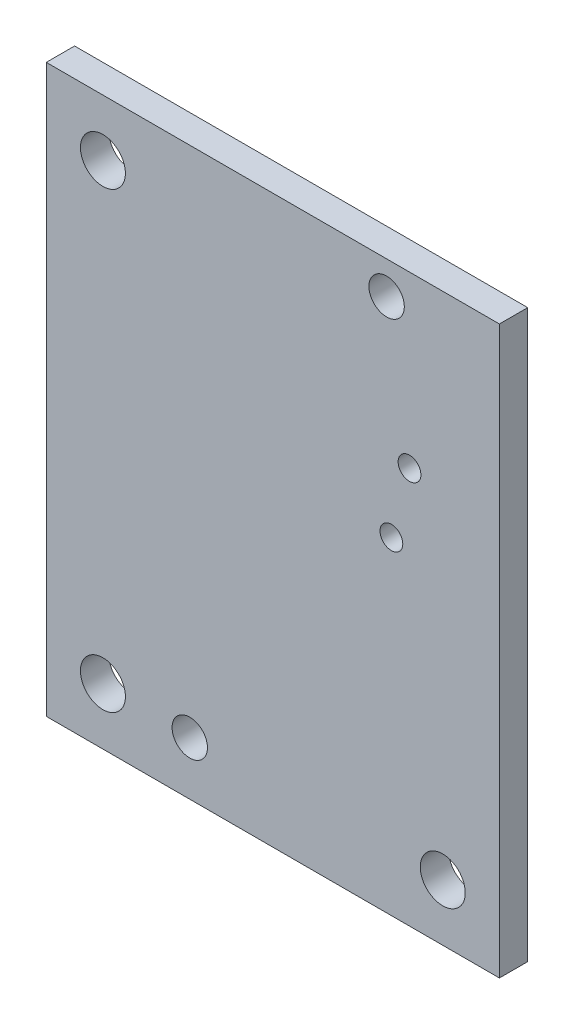
SolidWorks part; units mm, degrees
ref_plane "Front Plane" through (0, 0, 0) normal (1, 0, 0) x (0, 1, 0)
ref_plane "Top Plane" through (0, 0, 0) normal (0, 0, 1) x (0, 1, 0)
ref_plane "Right Plane" through (0, 0, 0) normal (0, 1, 0) x (-1, 0, 0)
sketch "Sketch2" plane through (0, 0, 0) normal (0, 0, 1) x (0, 1, 0)
  line L1 (0, 0) -> (127, 0)
  line L2 (0, 0) -> (0, 101.6)
  line L3 (0, 101.6) -> (127, 101.6)
  line L4 (127, 0) -> (127, 101.6)
  line L5 (12.7, 88.9) -> (114.3, 88.9) construction
  line L6 (12.7, 88.9) -> (12.7, 12.7) construction
  line L7 (12.7, 12.7) -> (114.3, 12.7) construction
  line L8 (114.3, 88.9) -> (114.3, 12.7) construction
  line L9 (12.7, 12.7) -> (73.436, 12.7) construction
  line L10 (12.7, 12.7) -> (12.7, 24.2176) construction
  line L11 (12.7, 24.2176) -> (73.436, 24.2176) construction
  line L12 (73.436, 12.7) -> (73.436, 24.2176) construction
  line L13 (12.7, 12.7) -> (88.9, 12.7) construction
  line L14 (12.7, 12.7) -> (12.7, 20.1554) construction
  line L15 (12.7, 20.1554) -> (88.9, 20.1554) construction
  line L16 (88.9, 12.7) -> (88.9, 20.1554) construction
  point P12 (12.7, 45.9336)
  point P16 (85.9042, 45.6317)
  dimension "D1" = 12.7
  dimension "D2" = 12.7
  dimension "D3" = 12.7
  dimension "D4" = 12.7
  dimension "D5" = 127
  dimension "D6" = 101.6
  dimension "D7" = 11.5176
  dimension "D8" = 60.736
  dimension "D9" = 7.4554
  dimension "D10" = 76.2
extrude "Boss-Extrude1" add sketch "Sketch2" along normal blind 6.35
hole_wizard "3/8 Clearance Hole1" positions "Sketch3" profile "Sketch4" hole size "3/8" standard "ANSI Inch" end condition through all
sketch "Sketch3" plane through (0, 0, 6.35) normal (0, 0, 1) x (1, 0, 0)
  point P0 (-12.7, 12.7)
  point P3 (-88.9, 12.7)
  point P6 (-88.9, 114.3)
sketch "Sketch4" plane through (-12.7, 12.7, 6.35) normal (1, 0, 0) x (0, -1, 0)
  line L0 (0, 0) -> (0, 6.35)
  line L1 (0, 6.35) -> (5.0419, 6.35)
  line L2 (5.0419, 6.35) -> (5.0419, 0)
  line L5 (5.0419, 0) -> (0, 0)
  line L11 (0, -6.35) -> (0, 107.95) construction
  dimension "Thru Hole Dia." = 10.0838
  dimension "Thru Hole Depth" = 6.35
hole_wizard "Tap Drill for 1/4-20 Tap1" positions "Sketch7" profile "Sketch6" hole size "1/4-20" standard "ANSI Inch" end condition through all
sketch "Sketch7" plane through (0, 0, 6.35) normal (0, 0, 1) x (1, 0, 0)
  point P0 (-24.2176, 73.436)
  point P3 (-20.1554, 88.9)
sketch "Sketch6" plane through (-24.2176, 73.436, 6.35) normal (1, 0, 0) x (0, -1, 0)
  line L0 (0, 0) -> (0, 6.35)
  line L1 (0, 6.35) -> (2.5527, 6.35)
  line L2 (2.5527, 6.35) -> (2.5527, 0)
  line L5 (2.5527, 0) -> (0, 0)
  line L11 (0, -6.35) -> (0, 107.95) construction
  dimension "Thru Hole Dia." = 5.1054
  dimension "Thru Hole Depth" = 6.35
sketch "Sketch8" plane through (0, 0, 6.35) normal (0, 0, 1) x (1, 0, 0)
  line L0 (-24.2176, 73.436) -> (-101.6, 3.0728) construction
  line L1 (-20.1554, 88.9) -> (-50.3098, 127) construction
  line L2 (0, 0) -> (0, 127) construction
  line L3 (-101.6, 127) -> (-101.6, 0) construction
  line L6 (0, 127) -> (-101.6, 127) construction
  line L7 (-80.0902, 22.6315) -> (-69.4261, 11.9674) construction
  line L8 (-37.1136, 110.3266) -> (-25.288, 119.686) construction
  point P12 (-28.2459, 123.4234)
  point P13 (-27.986, 123.095)
  dimension "D1" = 38.36
  dimension "D2" = 47.72
  dimension "D3" = 15.0812
  dimension "D4" = 15.0812
hole_wizard "Tap Drill for 3/8-16 Tap2" positions "Sketch9" profile "Sketch10" hole size "3/8-16" standard "ANSI Inch"
sketch "Sketch9" plane through (0, 0, 6.35) normal (0, 0, 1) x (1, 0, 0)
  point P0 (-69.4261, 11.9674)
  point P3 (-25.288, 119.686)
sketch "Sketch10" plane through (-69.4261, 11.9674, 6.35) normal (1, 0, 0) x (0, -1, 0)
  line L0 (0, 0) -> (0, 15.0847)
  line L1 (0, 15.0847) -> (3.9687, 12.7)
  line L2 (3.9687, 12.7) -> (3.9687, 0)
  line L5 (3.9687, 0) -> (0, 0)
  line L10 (0, 15.0847) -> (-3.9688, 12.7) construction
  line L11 (0, -6.35) -> (0, 107.95) construction
  dimension "Hole Dia." = 7.9375
  dimension "Hole Depth" = 12.7
  dimension "Drill Angle" = 118
